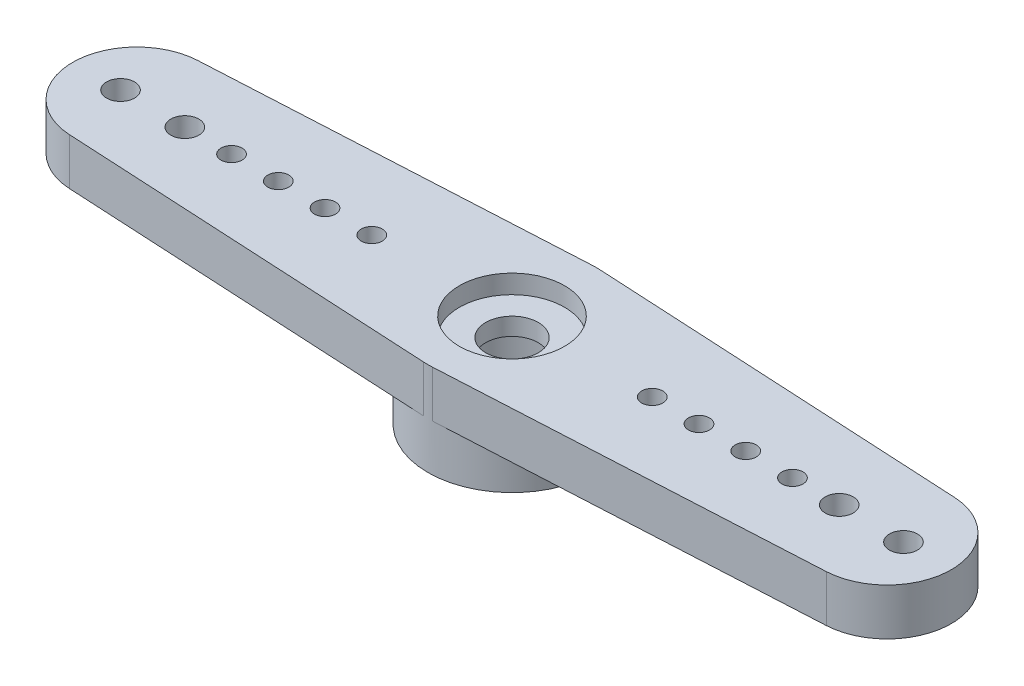
SolidWorks part; units mm, degrees
material "PA Type 6"
ref_plane "Front Plane" through (0, 0, 0) normal (0, 0, 1) x (1, 0, 0)
ref_plane "Top Plane" through (0, 0, 0) normal (0, 1, 0) x (1, 0, 0)
ref_plane "Right Plane" through (0, 0, 0) normal (1, 0, 0) x (0, 0, -1)
ref_axis "X-Axis" through (-88.99, 0, 0) along (1, 0, 0)
ref_axis "Y-Axis" through (0, 0, -88.99) along (0, 0, 1)
ref_axis "Z-Axis" through (0, 55, 0) along (0, -1, 0)
sketch "Sketch2" plane through (0, 0, 0) normal (0, 0, 1) x (1, 0, 0)
  line L0 (0, 0) -> (0, -2) construction
  line L1 (2.25, 2) -> (2.25, 1.2)
  line L2 (2.25, 1.2) -> (1.125, 1.2)
  line L3 (1.125, 1.2) -> (1.125, 0.45)
  line L4 (1.125, 0.45) -> (2.425, 0.45)
  line L5 (2.425, 0.45) -> (2.425, -2)
  line L6 (2.425, -2) -> (3.6, -2)
  line L7 (3.6, -2) -> (3.6, 2)
  line L8 (3.6, 2) -> (2.25, 2)
  dimension "D1" = 4.85
  dimension "D2" = 2.25
  dimension "D3" = 4.5
  dimension "D4" = 0.8
  dimension "D5" = 7.2
  dimension "D6" = 2
  dimension "D7" = 2.45
  dimension "D8" = 4
revolve "Revolve1" add sketch "Sketch2" angle 360 about axis through (0, 55, 0) along (0, -1, 0)
sketch "Sketch3" plane through (0, 0, 0) normal (0, 1, 0) x (1, 0, 0)
  line L0 (-16.75, 0) -> (16.75, 0) construction
  line L1 (0.1907, -3.5949) -> (16.1956, -2.7461)
  line L2 (16.1956, 2.7461) -> (0.1907, 3.5949)
  line L3 (-0.1907, 3.5949) -> (-16.1956, 2.7461)
  line L4 (-16.1956, -2.7461) -> (-0.1907, -3.5949)
  circle A0 centre (-16.75, 0) radius 0.6
  circle A1 centre (16.75, 0) radius 0.6
  circle A2 centre (-14, 0) radius 0.6
  circle A3 centre (14, 0) radius 0.6
  circle A4 centre (-12, 0) radius 0.45
  circle A5 centre (-10, 0) radius 0.45
  circle A6 centre (-8, 0) radius 0.45
  circle A7 centre (-6, 0) radius 0.45
  circle A8 centre (6, 0) radius 0.45
  circle A9 centre (8, 0) radius 0.45
  circle A10 centre (10, 0) radius 0.45
  circle A11 centre (12, 0) radius 0.45
  arc A12 (16.1956, -2.7461) -> (16.1956, 2.7461) centre (16.05, 0) ccw
  arc A13 (0.1907, 3.5949) -> (-0.1907, 3.5949) centre (0, 0) ccw
  arc A14 (-16.1956, 2.7461) -> (-16.1956, -2.7461) centre (-16.05, 0) ccw
  arc A15 (-0.1907, -3.5949) -> (0.1907, -3.5949) centre (0, 0) ccw
  circle A16 centre (0, 0) radius 2.425
  circle A17 centre (0, 0) radius 2.425 construction
  point P25 (18.8, 0)
  point P38 (-18.8, 0)
  dimension "D2" = 1.2
  dimension "D5" = 0.9
  dimension "D15" = 3.6
  dimension "D16" = 2.75
  dimension "D1" = 33.5
  dimension "D3" = 14
  dimension "D4" = 14
  dimension "D6" = 12
  dimension "D7" = 10
  dimension "D8" = 8
  dimension "D9" = 6
  dimension "D10" = 6
  dimension "D11" = 8
  dimension "D12" = 10
  dimension "D13" = 12
  dimension "D14" = 37.6
extrude "Boss-Extrude1" add sketch "Sketch3" along normal up to surface (2 mm away) up to face at (0, 2, 2.25)
